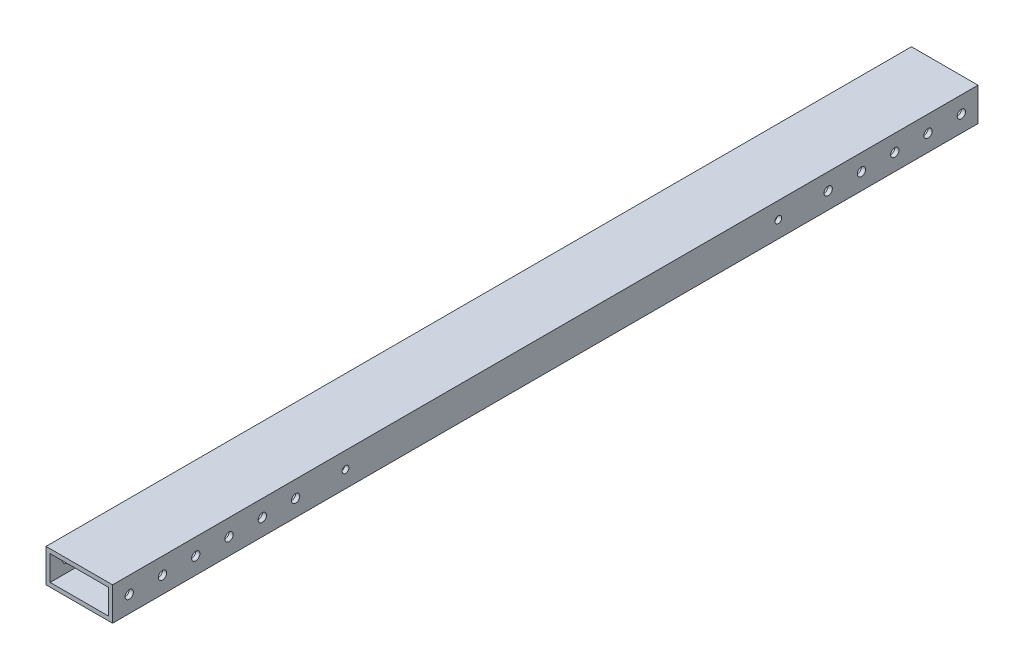
SolidWorks part; units mm, degrees
material "6061 Alloy"
ref_plane "Front Plane" through (0, 0, 0) normal (0, 0, 1) x (1, 0, 0)
ref_plane "Top Plane" through (0, 0, 0) normal (0, 1, 0) x (1, 0, 0)
ref_plane "Right Plane" through (0, 0, 0) normal (1, 0, 0) x (0, 0, -1)
sketch "Sketch1" plane through (0, 0, 0) normal (0, 0, 1) x (1, 0, 0)
  line L0 (-22.225, 9.525) -> (22.225, 9.525)
  line L2 (-25.4, 12.7) -> (25.4, 12.7)
  line L3 (-25.4, 12.7) -> (-25.4, -12.7)
  line L4 (-25.4, -12.7) -> (25.4, -12.7)
  line L5 (25.4, 12.7) -> (25.4, -12.7)
  line L10 (22.225, 9.525) -> (22.225, -9.525)
  line L11 (-22.225, -9.525) -> (22.225, -9.525)
  line L12 (-22.225, 9.525) -> (-22.225, -9.525)
  point P12 (0, 12.7)
  point P14 (25.4, 0)
  dimension "Wall Thickness" = 3.175
  dimension "Outside Width" = 50.8
  dimension "Outside Height" = 25.4
  dimension "Inside Height" = 19.05
  dimension "Inside Width" = 44.45
sketch "Sketch2" plane through (0, 0, 0) normal (1, 0, 0) x (0, 0, -1)
  line L0 (330.2, 0) -> (-330.2, 0)
  point P4 (0, 0)
  point P7 (-330.2, 0)
  point P10 (330.2, 0)
  dimension "Length" = 660.4
sketch "Sketch3" plane through (0, 0, 0) normal (0, 0, 1) x (1, 0, 0)
  line L21 (25.4, 12.7) -> (-25.4, 12.7)
  line L22 (25.4, -12.7) -> (25.4, 12.7)
  line L23 (-25.4, -12.7) -> (25.4, -12.7)
  line L24 (-25.4, 12.7) -> (-25.4, -12.7)
  line L25 (25.4, 12.7) -> (-25.4, 12.7)
  line L26 (25.4, -12.7) -> (25.4, 12.7)
  line L27 (-25.4, -12.7) -> (25.4, -12.7)
  line L28 (-25.4, 12.7) -> (-25.4, -12.7)
  line L29 (22.225, 9.525) -> (-22.225, 9.525)
  line L30 (22.225, -9.525) -> (22.225, 9.525)
  line L31 (-22.225, -9.525) -> (22.225, -9.525)
  line L32 (-22.225, 9.525) -> (-22.225, -9.525)
  line L33 (22.225, 9.525) -> (-22.225, 9.525)
  line L34 (22.225, -9.525) -> (22.225, 9.525)
  line L35 (-22.225, -9.525) -> (22.225, -9.525)
  line L36 (-22.225, 9.525) -> (-22.225, -9.525)
  dimension "D1" = 0
  dimension "D2" = 0
extrude "Boss-Extrude1" add sketch "Sketch3" along normal up to vertex (330.2 mm away) and the other way up to vertex (330.2 mm away) up to point (0, 0, 330.2) other way up to point (0, 0, -330.2)
sketch "Drawing Reference" plane through (0, 0, 0) normal (1, 0, 0) x (0, 0, -1)
  line L0 (-330.2, 0) -> (330.2, 0) construction
  line L1 (0, -12.7) -> (0, 12.7) construction
  line L2 (-330.2, -12.7) -> (330.2, -12.7) construction
  line L5 (-330.2, 12.7) -> (330.2, 12.7) construction
  point P7 (-293.624, 0)
  point P8 (293.624, 0)
  dimension "D1" = 36.576
sketch "Sketch5" plane through (25.4, 0, 0) normal (1, 0, 0) x (0, 0, -1)
  line L2 (-266.7, 0) -> (-241.3, 0)
  line L3 (-241.3, 0) -> (-215.9, 0)
  line L4 (-215.9, 0) -> (-190.5, 0)
  line L5 (-317.5, 0) -> (-330.2, 0)
  line L6 (-330.2, -12.7) -> (-330.2, 12.7) construction
  line L7 (-317.5, 0) -> (-292.1, 0)
  line L8 (-292.1, 0) -> (-266.7, 0)
sketch "Sketch8" plane through (25.4, 0, 0) normal (1, 0, 0) x (0, 0, -1)
  line L0 (330.2, 0) -> (292.1, 0)
  line L1 (330.2, -12.7) -> (330.2, 12.7) construction
  line L2 (292.1, 0) -> (266.7, 0)
  line L3 (266.7, 0) -> (241.3, 0)
  line L4 (241.3, 0) -> (215.9, 0)
  line L5 (330.2, 0) -> (317.5, 0)
hole_wizard "1/4 (0.25) Diameter Hole3" positions "Sketch12" profile "Sketch13" hole size "1/4" standard "ANSI Inch" end condition through all
sketch "Sketch12" plane through (-25.4, 0, 0) normal (-1, 0, 0) x (0, 0, 1)
  point P4 (-317.5, 0)
sketch "Sketch13" plane through (-25.4, 0, -317.5) normal (0, 1, 0) x (0, 0, 1)
  line L0 (0, 0) -> (0, 50.8)
  line L1 (0, 50.8) -> (3.175, 50.8)
  line L2 (3.175, 50.8) -> (3.175, 0)
  line L5 (3.175, 0) -> (0, 0)
  line L11 (0, -6.35) -> (0, 107.95) construction
  dimension "Thru Hole Dia." = 6.35
  dimension "Thru Hole Depth" = 50.8
hole_wizard "1/4 (0.25) Diameter Hole4" positions "Sketch14" profile "Sketch15" hole size "1/4" standard "ANSI Inch" end condition through all
sketch "Sketch14" plane through (-25.4, 0, 0) normal (-1, 0, 0) x (0, 0, 1)
  point P0 (292.1, 0)
  point P3 (317.5, 0)
sketch "Sketch15" plane through (-25.4, 0, 292.1) normal (0, 1, 0) x (0, 0, 1)
  line L0 (0, 0) -> (0, 50.8)
  line L1 (0, 50.8) -> (3.175, 50.8)
  line L2 (3.175, 50.8) -> (3.175, 0)
  line L5 (3.175, 0) -> (0, 0)
  line L11 (0, -6.35) -> (0, 107.95) construction
  dimension "Thru Hole Dia." = 6.35
  dimension "Thru Hole Depth" = 50.8
hole_wizard "1/4 (0.25) Diameter Hole5" positions "Sketch17" profile "Sketch18" hole size "1/4" standard "ANSI Inch" end condition through all
sketch "Sketch17" plane through (25.4, 0, 0) normal (1, 0, 0) x (0, 0, -1)
  point P0 (292.1, 0)
  point P3 (266.7, 0)
sketch "Sketch18" plane through (25.4, 0, -292.1) normal (0, 1, 0) x (0, 0, -1)
  line L0 (0, 0) -> (0, 50.8)
  line L1 (0, 50.8) -> (3.175, 50.8)
  line L2 (3.175, 50.8) -> (3.175, 0)
  line L5 (3.175, 0) -> (0, 0)
  line L11 (0, -6.35) -> (0, 107.95) construction
  dimension "Thru Hole Dia." = 6.35
  dimension "Thru Hole Depth" = 50.8
hole_wizard "1/4 (0.25) Diameter Hole6" positions "Sketch19" profile "Sketch20" hole size "1/4" standard "ANSI Inch" end condition through all
sketch "Sketch19" plane through (25.4, 0, 0) normal (1, 0, 0) x (0, 0, -1)
  point P0 (215.9, 0)
  point P3 (241.3, 0)
sketch "Sketch20" plane through (25.4, 0, -215.9) normal (0, 1, 0) x (0, 0, -1)
  line L0 (0, 0) -> (0, 50.8)
  line L1 (0, 50.8) -> (3.175, 50.8)
  line L2 (3.175, 50.8) -> (3.175, 0)
  line L5 (3.175, 0) -> (0, 0)
  line L11 (0, -6.35) -> (0, 107.95) construction
  dimension "Thru Hole Dia." = 6.35
  dimension "Thru Hole Depth" = 50.8
hole_wizard "1/4 (0.25) Diameter Hole7" positions "Sketch21" profile "Sketch22" hole size "1/4" standard "ANSI Inch" end condition through all
sketch "Sketch21" plane through (25.4, 0, 0) normal (1, 0, 0) x (0, 0, -1)
  point P0 (-190.5, 0)
  point P3 (-215.9, 0)
sketch "Sketch22" plane through (25.4, 0, 190.5) normal (0, 1, 0) x (0, 0, -1)
  line L0 (0, 0) -> (0, 50.8)
  line L1 (0, 50.8) -> (3.175, 50.8)
  line L2 (3.175, 50.8) -> (3.175, 0)
  line L5 (3.175, 0) -> (0, 0)
  line L11 (0, -6.35) -> (0, 107.95) construction
  dimension "Thru Hole Dia." = 6.35
  dimension "Thru Hole Depth" = 50.8
hole_wizard "1/4 (0.25) Diameter Hole8" positions "Sketch23" profile "Sketch24" hole size "1/4" standard "ANSI Inch" end condition through all
sketch "Sketch23" plane through (25.4, 0, 0) normal (1, 0, 0) x (0, 0, -1)
  point P0 (-266.7, 0)
  point P3 (-241.3, 0)
sketch "Sketch24" plane through (25.4, 0, 266.7) normal (0, 1, 0) x (0, 0, -1)
  line L0 (0, 0) -> (0, 50.8)
  line L1 (0, 50.8) -> (3.175, 50.8)
  line L2 (3.175, 50.8) -> (3.175, 0)
  line L5 (3.175, 0) -> (0, 0)
  line L11 (0, -6.35) -> (0, 107.95) construction
  dimension "Thru Hole Dia." = 6.35
  dimension "Thru Hole Depth" = 50.8
sketch "Sketch25" plane through (25.4, 0, 0) normal (1, 0, 0) x (0, 0, -1)
  line L0 (-190.5, 0) -> (-152.4, 0)
  line L1 (215.9, 0) -> (177.8, 0)
hole_wizard "13/64 (0.20313) Diameter Hole1" positions "Sketch26" profile "Sketch27" hole size "13/64" standard "ANSI Inch" end condition through all
sketch "Sketch26" plane through (25.4, 0, 0) normal (1, 0, 0) x (0, 0, -1)
  point P0 (-152.4, 0)
  point P3 (177.8, 0)
sketch "Sketch27" plane through (25.4, 0, 152.4) normal (0, 1, 0) x (0, 0, -1)
  line L0 (0, 0) -> (0, 50.8)
  line L1 (0, 50.8) -> (2.5798, 50.8)
  line L2 (2.5798, 50.8) -> (2.5798, 0)
  line L5 (2.5798, 0) -> (0, 0)
  line L11 (0, -6.35) -> (0, 107.95) construction
  dimension "Thru Hole Dia." = 5.1595
  dimension "Thru Hole Depth" = 50.8
hole_wizard "1/2 (0.5) Diameter Hole1" positions "Sketch33" profile "Sketch34" hole size "1/2" standard "ANSI Inch"
sketch "Sketch33" plane through (-25.4, 0, 0) normal (-1, 0, 0) x (0, 0, 1)
  point P0 (-146.05, 0)
  point P3 (120.65, 0)
sketch "Sketch34" plane through (-25.4, 0, -146.05) normal (0, 1, 0) x (0, 0, 1)
  line L0 (0, 0) -> (0, 10.1655)
  line L1 (0, 10.1655) -> (6.35, 6.35)
  line L2 (6.35, 6.35) -> (6.35, 0)
  line L5 (6.35, 0) -> (0, 0)
  line L10 (0, 10.1655) -> (-6.35, 6.35) construction
  line L11 (0, -6.35) -> (0, 107.95) construction
  dimension "Hole Dia." = 12.7
  dimension "Hole Depth" = 6.35
  dimension "Drill Angle" = 118
equation "\"D1@Drawing Reference\"=\"Outside Width@Sketch1\" * 0.72"
